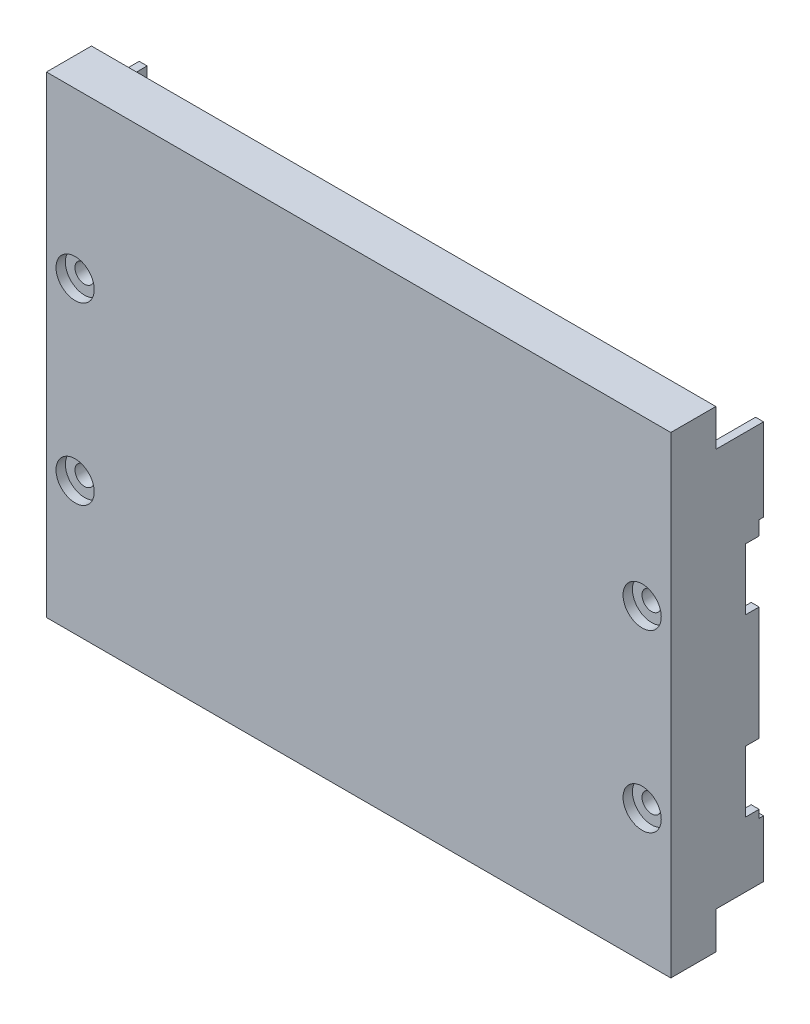
SolidWorks part; units mm, degrees
ref_plane "Front Plane" through (0, 0, 0) normal (0, 0, 1) x (1, 0, 0)
ref_plane "Top Plane" through (0, 0, 0) normal (0, 1, 0) x (1, 0, 0)
ref_plane "Right Plane" through (0, 0, 0) normal (1, 0, 0) x (0, 0, -1)
sketch "Sketch1" plane through (0, 0, 0) normal (0, 0, 1) x (1, 0, 0)
  line L0 (-30.5002, 35.0258) -> (66.0198, 35.0258) construction
  line L1 (67.5438, 35.0258) -> (-32.0242, 35.0258)
  line L2 (67.5438, 35.0258) -> (67.5438, -28.4742)
  line L3 (67.5438, -28.4742) -> (-32.0242, -28.4742)
  line L4 (-32.0242, 35.0258) -> (-32.0242, -28.4742)
  line L5 (66.0198, -28.4742) -> (-30.5002, -28.4742) construction
  line L7 (66.0198, 35.0258) -> (66.0198, -28.4742) construction
  line L8 (-30.5002, -28.4742) -> (-30.5002, 35.0258) construction
  dimension "D1" = 1.524
  dimension "D2" = 1.524
extrude "base" add sketch "Sketch1" along normal blind 5.08
sketch "Sketch2" plane through (0, 0, 0) normal (0, 0, -1) x (-1, 0, 0)
  line L0 (-67.5438, 35.0258) -> (32.0242, 35.0258) construction
  line L1 (30.5002, -26.9502) -> (-66.0198, -26.9502)
  line L2 (30.5002, -26.9502) -> (30.5002, 33.5018)
  line L3 (30.5002, 33.5018) -> (-66.0198, 33.5018)
  line L4 (-66.0198, -26.9502) -> (-66.0198, 33.5018)
  line L5 (-67.5438, -28.4742) -> (-67.5438, 35.0258) construction
  line L6 (32.0242, -28.4742) -> (-67.5438, -28.4742) construction
  line L7 (32.0242, 35.0258) -> (32.0242, -28.4742) construction
  dimension "D1" = 1.524
  dimension "D2" = 1.524
  dimension "D3" = 1.524
  dimension "D4" = 1.524
extrude "hollow" cut sketch "Sketch2" against normal blind 2
sketch "Sketch3" plane through (0, 0, 0) normal (0, 0, -1) x (-1, 0, 0)
  line L0 (-67.5438, 35.0258) -> (32.0242, 35.0258) construction
  line L1 (30.7542, 35.0258) -> (32.0242, 35.0258)
  line L2 (30.7542, 35.0258) -> (30.7542, -28.4742)
  line L3 (30.7542, -28.4742) -> (32.0242, -28.4742)
  line L4 (32.0242, 35.0258) -> (32.0242, -28.4742)
  line L5 (32.0242, -28.4742) -> (-67.5438, -28.4742) construction
  line L7 (32.0242, 35.0258) -> (32.0242, -28.4742) construction
  line L9 (-67.5438, 35.0258) -> (-66.2738, 35.0258)
  line L10 (-67.5438, 35.0258) -> (-67.5438, -28.4742)
  line L11 (-67.5438, -28.4742) -> (-66.2738, -28.4742)
  line L12 (-66.2738, 35.0258) -> (-66.2738, -28.4742)
  dimension "D1" = 1.27
  dimension "D2" = 1.27
extrude "end pieces" add sketch "Sketch3" along normal blind 9
sketch "Sketch7" plane through (67.5438, 0, 0) normal (1, 0, 0) x (0, 0, -1)
  line L0 (9, 35.0258) -> (9, -28.4742) construction
  line L1 (6.7986, 9.8068) -> (9, 9.8068)
  line L2 (6.7986, 9.8068) -> (6.7986, 19.6048)
  line L3 (6.7986, 19.6048) -> (9, 19.6048)
  line L4 (9, 9.8068) -> (9, 19.6048)
  line L5 (6.9986, 19.4048) -> (16.7986, 19.4048) construction
  line L6 (6.9986, 19.4048) -> (6.9986, 10.0068) construction
  line L7 (6.9986, 10.0068) -> (16.7986, 10.0068) construction
  line L8 (6.9986, -17.9332) -> (16.7986, -17.9332) construction
  line L9 (6.7986, -18.1332) -> (9, -18.1332)
  line L10 (6.7986, -18.1332) -> (6.7986, -8.3352)
  line L11 (6.7986, -8.3352) -> (9, -8.3352)
  line L12 (9, -18.1332) -> (9, -8.3352)
  dimension "D1" = 0.2
  dimension "D2" = 0.2
  dimension "D3" = 0.2
  dimension "D4" = 0.2
extrude "where top intrudes" cut sketch "Sketch7" against normal through all
sketch "cable stop wings alt" plane through (0, 0, 5.08) normal (0, 0, 1) x (1, 0, 0)
  line L1 (-32.0242, -28.4742) -> (67.5438, -28.4742)
  line L2 (-32.0242, -28.4742) -> (-32.0242, -33.4742)
  line L3 (-32.0242, -33.4742) -> (67.5438, -33.4742)
  line L4 (67.5438, -28.4742) -> (67.5438, -33.4742)
  line L5 (67.5438, 35.0258) -> (-32.0242, 35.0258) construction
  line L6 (-32.0242, -28.4742) -> (67.5438, -28.4742) construction
  line L8 (-32.0242, 35.0258) -> (67.5438, 35.0258)
  line L9 (-32.0242, 35.0258) -> (-32.0242, 40.0258)
  line L10 (-32.0242, 40.0258) -> (67.5438, 40.0258)
  line L11 (67.5438, 35.0258) -> (67.5438, 40.0258)
  line L12 (67.5438, -28.4742) -> (67.5438, 35.0258) construction
  line L13 (-32.0242, 35.0258) -> (-32.0242, -28.4742) construction
  dimension "D1" = 5
extrude "cable stop wing boss alt" add sketch "cable stop wings alt" against normal blind 1.5
sketch "Sketch4" plane through (0, 0, 2) normal (0, 0, -1) x (-1, 0, 0)
  circle A0 centre (-62.9718, 14.7058) radius 3.175
  circle A1 centre (-62.9718, -13.2342) radius 3.175
  circle A2 centre (27.4522, -13.2342) radius 3.175
  circle A4 centre (27.4522, 14.7058) radius 3.175
  dimension "D1" = 6.35
extrude "screw bosses" add sketch "Sketch4" along normal up to surface (2 mm away) up to face at (17.7598, 3.2758, 0)
sketch "Sketch5" plane through (0, 0, 0) normal (0, 0, -1) x (-1, 0, 0)
  circle A0 centre (-62.9718, 14.7058) radius 1.524
  circle A1 centre (-62.9718, -13.2342) radius 1.524
  circle A2 centre (27.4522, 14.7058) radius 1.524
  circle A3 centre (27.4522, -13.2342) radius 1.524
extrude "screw holes" cut sketch "Sketch5" against normal through all
sketch "Sketch6" plane through (0, 0, 5.08) normal (0, 0, 1) x (1, 0, 0)
  circle A0 centre (62.9718, -13.2342) radius 3.048
  circle A1 centre (62.9718, 14.7058) radius 3.048
  circle A2 centre (-27.4522, -13.2342) radius 3.048
  circle A4 centre (-27.4522, 14.7058) radius 3.048
extrude "counter sink" cut sketch "Sketch6" against normal blind 1.5
sketch "Sketch25" plane through (0, 0, 5.08) normal (0, 0, 1) x (1, 0, 0)
  line L1 (-32.0242, 40.9458) -> (67.5438, 40.9458)
  line L2 (-32.0242, 40.9458) -> (-32.0242, 36.4458)
  line L3 (-32.0242, 36.4458) -> (67.5438, 36.4458)
  line L4 (67.5438, 40.9458) -> (67.5438, 36.4458)
  line L5 (-28.1176, 35.9458) -> (-26.1364, 35.9458) construction
  line L6 (-26.5479, -29.3942) -> (-28.5291, -29.3942) construction
  line L7 (67.5438, -34.3942) -> (-32.0242, -34.3942)
  line L8 (67.5438, -34.3942) -> (67.5438, -29.8942)
  line L9 (67.5438, -29.8942) -> (-32.0242, -29.8942)
  line L10 (-32.0242, -34.3942) -> (-32.0242, -29.8942)
  line L13 (-32.0242, 40.0258) -> (-32.0242, -33.4742) construction
  line L14 (67.5438, -33.4742) -> (67.5438, 40.0258) construction
  dimension "D1" = 0.5
  dimension "D2" = 5
  dimension "D3" = 0.5
  dimension "D4" = 5
extrude "box under connectors" add sketch "Sketch25" against normal offset from surface (7.1786 mm away) 3.81
sketch "Sketch26" plane through (-32.0242, 0, 0) normal (-1, 0, 0) x (0, 0, 1)
  line L0 (-2.0986, 40.9458) -> (5.08, 40.9458) construction
  line L1 (-2.0986, -34.3942) -> (5.08, -34.3942)
  line L2 (-2.0986, -34.3942) -> (-2.0986, 40.9458)
  line L3 (-2.0986, 40.9458) -> (5.08, 40.9458)
  line L4 (5.08, -34.3942) -> (5.08, 40.9458)
  line L5 (-2.0986, -34.3942) -> (5.08, -34.3942) construction
extrude "Fill ends" add sketch "Sketch26" against normal blind 1.5
extrude "Fill the other end" add sketch "Sketch26<2>" along normal blind 1.5 from surface starting at face at (67.5438, 2.2598, -3.2554)
sketch "Sketch26<2>" plane through (-32.0242, 0, 0) normal (-1, 0, 0) x (0, 0, 1) same geometry as "Sketch26"
sketch "Sketch27" plane through (-32.0242, 0, 0) normal (-1, 0, 0) x (0, 0, 1)
  line L0 (-10.2086, -28.4742) -> (-10.2086, -18.8862) construction
  line L1 (-9, -28.4742) -> (-9.7086, -28.4742)
  line L2 (-9, -28.4742) -> (-9, -19.3862)
  line L3 (-9, -19.3862) -> (-9.7086, -19.3862)
  line L4 (-9.7086, -28.4742) -> (-9.7086, -19.3862)
  line L5 (-9, -18.8862) -> (-10.2086, -18.8862) construction
  line L6 (-9, 21.3568) -> (-10.2086, 21.3568) construction
  line L7 (-9, 35.0258) -> (-9.7086, 35.0258)
  line L8 (-9, 35.0258) -> (-9, 21.8568)
  line L9 (-9, 21.8568) -> (-9.7086, 21.8568)
  line L10 (-9.7086, 35.0258) -> (-9.7086, 21.8568)
  line L11 (-10.2086, 21.3568) -> (-10.2086, 35.0258) construction
  dimension "D1" = 0.5
  dimension "D2" = 0.5
  dimension "D3" = 0.5
  dimension "D4" = 0.5
extrude "Boss-Extrude4" add sketch "Sketch27" against normal up to vertex (1.27 mm away) up to point (-30.7542, 35.0258, -9)
extrude "Boss-Extrude5" add sketch "Sketch27<2>" along normal up to vertex (-98.298 mm away) from surface up to point (66.2738, 35.0258, -9) starting at face at (67.5438, 2.0058, -4.9643)
sketch "Sketch27<2>" plane through (-32.0242, 0, 0) normal (-1, 0, 0) x (0, 0, 1) same geometry as "Sketch27"
